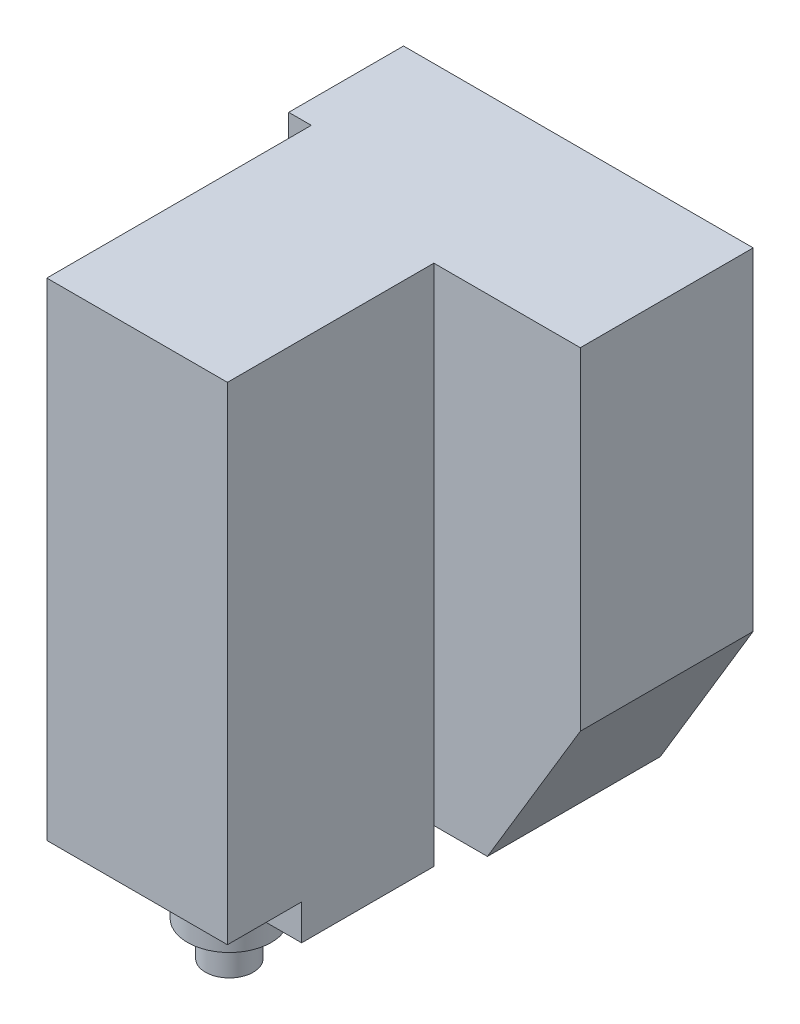
SolidWorks part; units mm, degrees
ref_plane "Front Plane" through (0, 0, 0) normal (0, 0, 1) x (1, 0, 0)
ref_plane "Top Plane" through (0, 0, 0) normal (0, 1, 0) x (1, 0, 0)
ref_plane "Right Plane" through (0, 0, 0) normal (1, 0, 0) x (0, 0, -1)
sketch "Sketch1" plane through (0, 0, 0) normal (0, 0, 1) x (1, 0, 0)
  line L0 (-280, 755) -> (-280, 0)
  line L1 (-280, 0) -> (0, 0)
  line L2 (0, 0) -> (0, 755)
  line L3 (-280, 755) -> (0, 755)
  point P3 (0, 0)
  dimension "D1" = 280
  dimension "D2" = 755
extrude "Boss-Extrude1" add sketch "Sketch1" along normal blind 588
sketch "Sketch4" plane through (0, 0, 0) normal (0, -1, 0) x (1, 0, 0)
  line L1 (-280, 588) -> (0, 588) construction
  line L5 (-280, 588) -> (-280, 0) construction
  circle A0 centre (-160, 425) radius 65
  circle A1 centre (-160, 425) radius 81
  circle A2 centre (-160, 425) radius 37
  dimension "D1" = 130
  dimension "D2" = 16
  dimension "D3" = 82
  dimension "D4" = 39
  dimension "D5" = 74
extrude "Boss-Extrude2" add sketch "Sketch4" along normal blind 20 contours A1
extrude "Boss-Extrude3" add sketch "Sketch4<3>" along normal blind 106 from surface contours A0 starting at face at (-160, -20, 344)
sketch "Sketch4<3>" plane through (0, 0, 0) normal (0, -1, 0) x (1, 0, 0) same geometry as "Sketch4"
extrude "Boss-Extrude4" add sketch "Sketch4<4>" along normal blind 54 from surface contours A2 region at (-160, 0, 425) starting at face at (-160, -126, 360)
sketch "Sketch4<4>" plane through (0, 0, 0) normal (0, -1, 0) x (1, 0, 0) same geometry as "Sketch4"
ref_plane "Plane1" through (0, 0, 268) normal (0, 0, 1) x (1, 0, 0)
sketch "Sketch5" plane through (0, 0, 268) normal (0, 0, -1) x (-1, 0, 0)
  line L0 (0, 0) -> (-83, 0)
  line L1 (-83, 0) -> (-227, 240.1333)
  line L2 (-227, 240.1333) -> (-227, 755)
  line L3 (-227, 755) -> (0, 755)
  line L4 (0, 755) -> (0, 0)
  line L5 (0, 755) -> (280, 755) construction
  dimension "D1" = 83
  dimension "D2" = 227
  dimension "D3" = 280
extrude "Boss-Extrude5" add sketch "Sketch5" along normal up to surface (268 mm away) contours L2 L3 L4 L0 L1 up to face at (-140, 377.5, 0)
ref_plane "Plane2" through (0, 0, 178) normal (0, 0, 1) x (1, 0, 0)
sketch "Sketch6" plane through (0, 0, 178) normal (0, 0, 1) x (1, 0, 0)
  line L0 (-315, -70) -> (-315, 755)
  line L1 (-315, 755) -> (-280, 755)
  line L2 (-280, 755) -> (-280, 0) construction
  line L3 (-280, 0) -> (0, 0) construction
  line L4 (-315, -70) -> (0, -70)
  line L5 (0, 0) -> (0, -70)
  line L6 (-280, 755) -> (-280, 0)
  line L7 (-280, 0) -> (0, 0)
  dimension "D1" = 35
  dimension "D2" = 70
extrude "Boss-Extrude6" add sketch "Sketch6" against normal up to surface (178 mm away) contours L7 L6 L1 L0 L4 L5 region at (-306.1691, 342.5, 178) up to face at (-4.6, 350.0267, 0)
sketch "Sketch7" plane through (0, 0, 0) normal (0, -1, 0) x (1, 0, 0)
  line L0 (-280, 588) -> (0, 588) construction
  line L1 (-55, 473) -> (0, 473)
  line L2 (-55, 473) -> (-55, 268)
  line L3 (-55, 268) -> (0, 268)
  line L4 (0, 473) -> (0, 268)
  line L5 (0, 588) -> (0, 268) construction
  line L6 (0, 268) -> (83, 268) construction
  dimension "D1" = 115
  dimension "D2" = 55
extrude "Boss-Extrude7" add sketch "Sketch7" along normal blind 55
sketch "Sketch8" plane through (0, -180, 0) normal (0, -1, 0) x (1, 0, 0)
  line L0 (-160, 425) -> (-62.2663, 425) construction
  line L1 (-160, 425) -> (-160, 569.1924) construction
  point P0 (-160, 425)
ref_plane "Plane3" through (-160, 0, 0) normal (-1, 0, 0) x (0, 0, 1)
